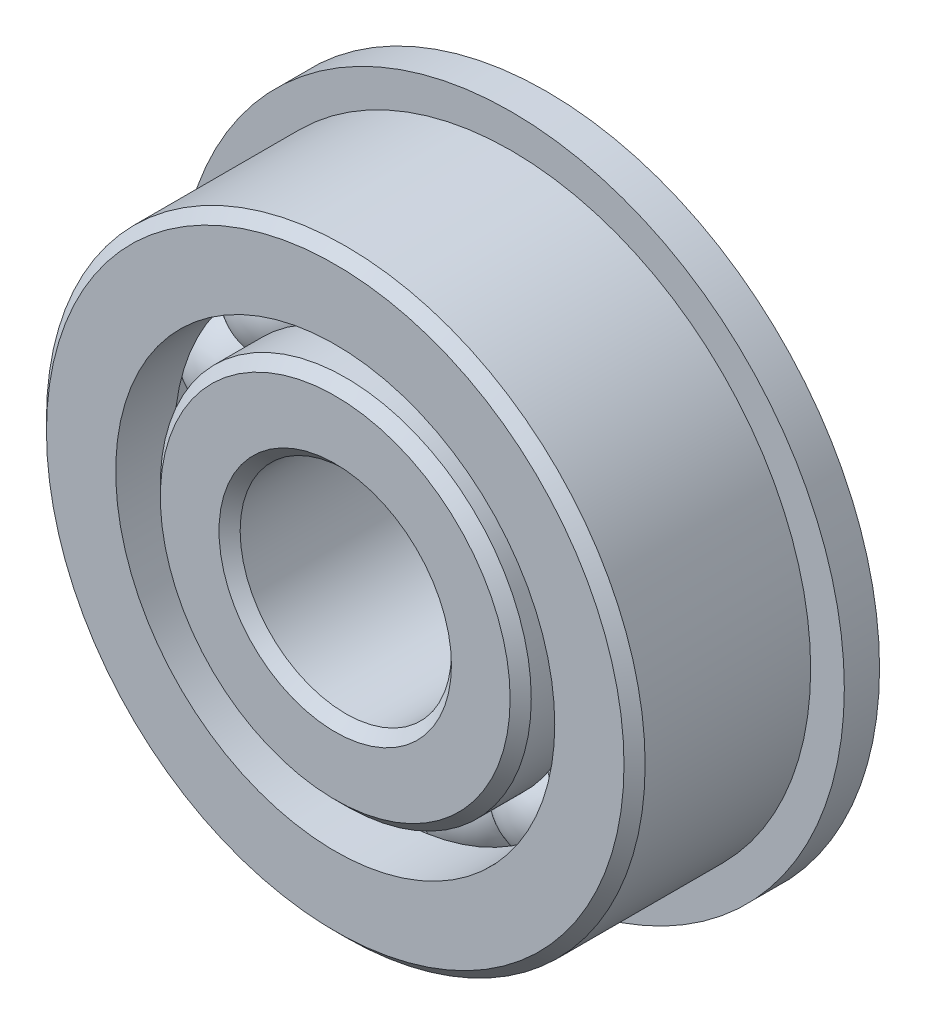
SolidWorks part; units mm, degrees
ref_plane "Front Plane" through (0, 0, 0) normal (0, 0, 1) x (1, 0, 0)
ref_plane "Top Plane" through (0, 0, 0) normal (0, 1, 0) x (1, 0, 0)
ref_plane "Right Plane" through (0, 0, 0) normal (1, 0, 0) x (0, 0, -1)
sketch "Sketch1" plane through (0, 0, 0) normal (1, 0, 0) x (0, 0, -1)
  line L0 (-4.7625, 0) -> (4.7625, 0) construction
  line L1 (0, 13.4937) -> (0, -13.4937) construction
  line L2 (4.2863, 13.4938) -> (-4.2863, 13.4937)
  line L3 (-4.2863, 13.4937) -> (-4.7625, 13.0175)
  line L4 (-4.7625, 13.0175) -> (-4.7625, 9.8957)
  line L5 (-4.7625, 9.8957) -> (-2.1167, 9.8957)
  line L6 (4.7625, 9.8957) -> (2.1167, 9.8957)
  line L7 (4.7625, 13.0175) -> (4.7625, 9.8957)
  line L8 (4.2863, 13.4938) -> (4.7625, 13.0175)
  line L9 (0, 13.4937) -> (0, 9.1281) construction
  line L10 (0, 9.1281) -> (0, 4.7625) construction
  arc A0 (-2.1167, 9.8957) -> (2.1167, 9.8957) centre (0, 9.1281) cw
  point P14 (0, 4.7625)
  dimension "Width" = 9.525
  dimension "OD" = 26.9875
  dimension "D1" = 45
  dimension "D2" = 0.4763
  dimension "D3" = 4.2333
  dimension "D4" = 0.7676
revolve "Revolve1" add sketch "Sketch1" angle 360 about L0
sketch "Sketch3" plane through (0, 0, 0) normal (1, 0, 0) x (0, 0, -1)
  line L0 (-2.1167, 8.3605) -> (-4.7625, 8.3605) construction
  line L1 (-4.7625, 13.0175) -> (-4.7625, 9.8957) construction
  line L2 (-4.2863, 13.4937) -> (-4.7625, 13.0175) construction
  line L3 (-4.7625, 8.3605) -> (-4.7625, 5.2388) construction
  line L4 (-4.7625, 5.2388) -> (-4.7625, 7.8843)
  line L5 (-4.7625, 5.2388) -> (-4.2863, 4.7625)
  line L6 (-4.2863, 4.7625) -> (5.8737, 4.7625)
  line L7 (-4.7625, 13.0175) -> (-4.7625, -13.0175) construction
  line L8 (5.8737, 4.7625) -> (6.35, 5.2388)
  line L10 (6.35, 5.2388) -> (6.35, 8.3605) construction
  line L11 (6.35, 8.3605) -> (2.1167, 8.3605) construction
  line L12 (0, 13.4937) -> (0, -13.4937) construction
  line L13 (4.2863, 13.4938) -> (4.7625, 13.0175) construction
  line L14 (-4.7625, 7.8843) -> (-4.2863, 8.3605)
  line L15 (-4.2863, 8.3605) -> (-2.1167, 8.3605)
  line L16 (2.1167, 8.3605) -> (5.8737, 8.3605)
  line L17 (5.8737, 8.3605) -> (6.35, 7.8843)
  line L18 (6.35, 7.8843) -> (6.35, 5.2388)
  arc A1 (2.1167, 8.3605) -> (-2.1167, 8.3605) centre (0, 9.1281) cw
  arc A2 (2.1167, 9.8957) -> (-2.1167, 9.8957) centre (0, 9.1281) ccw construction
  dimension "D1" = 45
  dimension "Ring Wd" = 11.1125
revolve "Revolve3" add sketch "Sketch3" angle 360 about L0
sketch "Sketch4" plane through (0, 0, 0) normal (1, 0, 0) x (0, 0, -1)
  line L0 (-2.2515, 9.1281) -> (2.2515, 9.1281)
  arc A2 (-2.2515, 9.1281) -> (2.2515, 9.1281) centre (0, 9.1281) cw
  arc A3 (2.1167, 9.8957) -> (-2.1167, 9.8957) centre (0, 9.1281) ccw construction
revolve "Revolve4" add sketch "Sketch4" angle 360 about L0
ref_axis "Axis1" through (0, 0, -4.7625) along (0, 0, 1)
pattern_circular "CirPattern1" count 15 every 24 about axis through (0, 0, -4.7625) along (0, 0, 1) of bodies 104
sketch "Sketch5" plane through (0, 0, 0) normal (1, 0, 0) x (0, 0, -1)
  line L0 (-4.7625, 9.8957) -> (-2.1167, 9.8957) construction
  line L1 (-4.5244, 9.8957) -> (-2.2515, 9.8957)
  line L2 (-4.5244, 9.8957) -> (-4.5244, 8.3605)
  line L3 (-4.5244, 8.3605) -> (-2.2515, 8.3605)
  line L4 (-2.2515, 9.8957) -> (-2.2515, 8.3605)
  line L5 (-2.1167, 8.3605) -> (-4.7625, 8.3605) construction
  line L6 (4.7625, 9.8957) -> (2.1167, 9.8957) construction
  line L7 (4.5244, 9.8957) -> (2.2515, 9.8957)
  line L8 (4.5244, 9.8957) -> (4.5244, 8.3605)
  line L9 (4.5244, 8.3605) -> (2.2515, 8.3605)
  line L10 (2.2515, 9.8957) -> (2.2515, 8.3605)
  line L11 (6.35, 8.3605) -> (2.1167, 8.3605) construction
  line L12 (-4.2863, 13.4937) -> (-4.7625, 13.0175) construction
  point P18 (-4.5244, 13.2556)
revolve "Revolve5" [suppressed] add sketch "Sketch5" angle 360 about L0
sketch "Sketch6" plane through (0, 0, 0) normal (1, 0, 0) x (0, 0, -1)
  line L1 (4.7625, 9.8957) -> (3.175, 9.8957)
  line L2 (4.7625, 9.8957) -> (4.7625, 15.0114)
  line L3 (4.7625, 15.0114) -> (3.175, 15.0114)
  line L4 (3.175, 9.8957) -> (3.175, 15.0114)
  line L5 (4.7625, 0) -> (-4.7625, 0) construction
  dimension "Flange OD" = 30.0228
  dimension "Th" = 1.5875
revolve "Revolve6" add sketch "Sketch6" angle 360 about L5
equation "\"D2@Sketch1\" = \"Width@Sketch1\"*.05"
equation "\"D3@Sketch1\" = \"Width@Sketch1\"/2.25"
equation "\"D4@Sketch1\" = (((\"OD@Sketch1\"-\"Width@Sketch1\")/2)/3.25)/3.5"
equation "\"D2@CirPattern1\" = 360/\"Balls@CirPattern1\""
